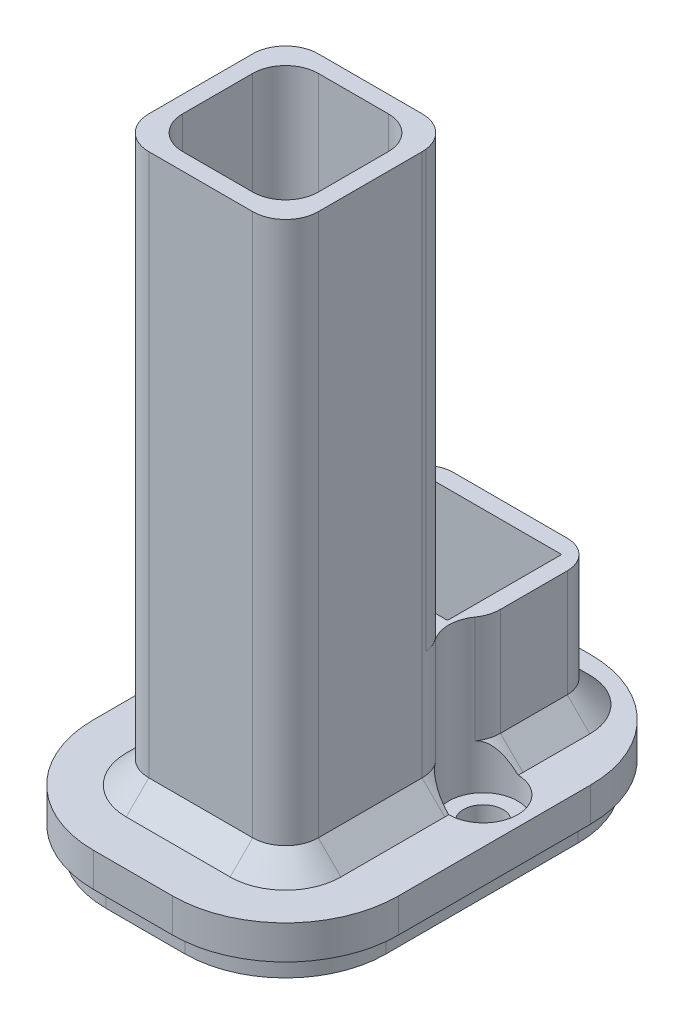
SolidWorks part; units mm, degrees
ref_plane "Front Plane" through (0, 0, 0) normal (0, 0, 1) x (1, 0, 0)
ref_plane "Top Plane" through (0, 0, 0) normal (0, 1, 0) x (1, 0, 0)
ref_plane "Right Plane" through (0, 0, 0) normal (1, 0, 0) x (0, 0, -1)
sketch "Sketch2" plane through (0, 0, 0) normal (0, 1, 0) x (1, 0, 0)
  line L0 (-7.55, 19.89) -> (7.55, 19.89)
  line L1 (-6.05, 8.29) -> (6.05, 8.29)
  line L2 (-6.05, 8.29) -> (-6.05, 18.39)
  line L3 (-6.05, 18.39) -> (6.05, 18.39)
  line L4 (0, -55) -> (0, 55) construction
  line L8 (13.5, -13.5) -> (13.5, 23.5)
  line L9 (13.5, 23.5) -> (-13.5, 23.5)
  line L10 (-13.5, 23.5) -> (-13.5, -13.5)
  line L11 (-13.5, -13.5) -> (13.5, -13.5)
  line L12 (6.05, 8.29) -> (6.05, 18.39)
  line L13 (-6.05, 8.29) -> (6.05, 18.39) construction
  line L14 (-6.05, 18.39) -> (6.05, 8.29) construction
  line L15 (7.55, 6.79) -> (7.55, 19.89)
  line L16 (-7.55, 6.79) -> (7.55, 6.79)
  line L17 (-7.55, 6.79) -> (-7.55, 19.89)
  circle A0 centre (0, 13.34) radius 4.25
  circle A1 centre (0, 0) radius 8.05
  circle A2 centre (-9.5, 8) radius 1.75
  circle A4 centre (9.5, 8) radius 1.75
  circle A5 centre (0, 0) radius 3
  point P2 (0, 13.34)
  point P16 (0, -10.5165)
  point P24 (0, -13.5)
  dimension "D5" = 8.5
  dimension "D6" = 16.1
  dimension "D10" = 8
  dimension "D8" = 3.5
  dimension "D12" = 6
  dimension "D2" = 12.1
  dimension "D3" = 10.1
  dimension "D1" = 37
  dimension "D7" = 27
  dimension "D9" = 10.16
  dimension "D11" = 4
  dimension "D4" = 1.5
extrude "Boss-Extrude1" add sketch "Sketch2" along normal blind 5 contours L10 L11 L8 L9 L16 L17 L0 L15 | L17 A2 | A4 | L16 A1 region at (0, 0, -6.571) region at (0, 0, 13.042) region at (-9.5, 0, -8) region at (9.5, 0, -8)
extrude "Boss-Extrude2" add sketch "Sketch2<7>" along normal blind 16.5 contours A1 L16 L15 L0 L17 L12 L1 L2 L3 | L16 A1 region at (0, 0, -19.6901) region at (0, 0, -7.2975)
sketch "Sketch2<7>" plane through (0, 0, 0) normal (0, 1, 0) x (1, 0, 0) same geometry as "Sketch2"
extrude "Boss-Extrude3" add sketch "Sketch2<8>" along normal blind 1 contours L1 L12 L3 L2 A0 region at (-5.8924, 0, -13.34)
sketch "Sketch2<8>" plane through (0, 0, 0) normal (0, 1, 0) x (1, 0, 0) same geometry as "Sketch2"
extrude "Cut-Extrude3" cut sketch "Sketch2<12>" along normal blind 4 contours L16 A1 | L16 A1 region at (0, 0, -7.2975) region at (0, 0, -6.571)
sketch "Sketch2<12>" plane through (0, 0, 0) normal (0, 1, 0) x (1, 0, 0) same geometry as "Sketch2"
extrude "Cut-Extrude2" cut sketch "Sketch2<11>" along normal through all contours A2 | A4 region at (-9.5, 0, -8) region at (9.5, 0, -8)
sketch "Sketch2<11>" plane through (0, 0, 0) normal (0, 1, 0) x (1, 0, 0) same geometry as "Sketch2"
fillet "Fillet1" radius 10 4 edges at (-13.5, 2.5, -23.5) (-13.5, 2.5, 13.5) (13.5, 2.5, 13.5) (13.5, 2.5, -23.5)
sketch "Sketch3" plane through (0, 0, 0) normal (0, -1, 0) x (1, 0, 0)
  line L4 (-12.4, 3.5) -> (-12.4, -13.5)
  line L5 (-3.5, -22.4) -> (3.5, -22.4)
  line L6 (12.4, -13.5) -> (12.4, 3.5)
  line L7 (3.5, 12.4) -> (-3.5, 12.4)
  line L12 (-13.5, 3.5) -> (-13.5, -13.5)
  line L13 (-3.5, -23.5) -> (3.5, -23.5)
  line L14 (13.5, -13.5) -> (13.5, 3.5)
  line L15 (3.5, 13.5) -> (-3.5, 13.5)
  line L16 (-13.5, 3.5) -> (-13.5, -13.5)
  line L17 (-3.5, -23.5) -> (3.5, -23.5)
  line L18 (13.5, -13.5) -> (13.5, 3.5)
  line L19 (3.5, 13.5) -> (-3.5, 13.5)
  arc A4 (-12.4, -13.5) -> (-3.5, -22.4) centre (-3.5, -13.5) ccw
  arc A5 (3.5, -22.4) -> (12.4, -13.5) centre (3.5, -13.5) ccw
  arc A6 (12.4, 3.5) -> (3.5, 12.4) centre (3.5, 3.5) ccw
  arc A7 (-3.5, 12.4) -> (-12.4, 3.5) centre (-3.5, 3.5) ccw
  arc A12 (-13.5, -13.5) -> (-3.5, -23.5) centre (-3.5, -13.5) ccw
  arc A14 (3.5, -23.5) -> (13.5, -13.5) centre (3.5, -13.5) ccw
  arc A16 (13.5, 3.5) -> (3.5, 13.5) centre (3.5, 3.5) ccw
  arc A17 (-3.5, 13.5) -> (-13.5, 3.5) centre (-3.5, 3.5) ccw
  arc A18 (-13.5, -13.5) -> (-3.5, -23.5) centre (-3.5, -13.5) ccw
  arc A19 (3.5, -23.5) -> (13.5, -13.5) centre (3.5, -13.5) ccw
  arc A20 (13.5, 3.5) -> (3.5, 13.5) centre (3.5, 3.5) ccw
  arc A22 (-3.5, 13.5) -> (-13.5, 3.5) centre (-3.5, 3.5) ccw
  dimension "D1" = 0
  dimension "D2" = 1.1
extrude "Cut-Extrude1" cut sketch "Sketch3" against normal blind 2
sketch "Sketch4" plane through (0, 5, 0) normal (0, 1, 0) x (1, 0, 0)
  line L0 (7.5, -7.5) -> (7.5, 7.5)
  line L1 (-6, -6) -> (6, -6)
  line L2 (-6, -6) -> (-6, 6)
  line L3 (-6, 6) -> (6, 6)
  line L4 (6, -6) -> (6, 6)
  line L5 (-6, -6) -> (6, 6) construction
  line L6 (-6, 6) -> (6, -6) construction
  line L7 (-7.5, 7.5) -> (7.5, 7.5)
  line L8 (-7.5, -7.5) -> (-7.5, 7.5)
  line L9 (-7.5, -7.5) -> (7.5, -7.5)
  line L10 (0, -9.075) -> (0, 9.075) construction
  circle A0 centre (-9.5, 8) radius 3.05
  circle A1 centre (9.5, 8) radius 3.05
  point P0 (0, 0)
  line M6 (7.55, 19.89) -> (7.55, 6.79)
  line M7 (7.55, 6.79) -> (-7.55, 6.79)
  line M8 (-7.55, 6.79) -> (-7.55, 19.89)
  circle M18 centre (9.5, 8) radius 1.75
  circle M19 centre (-9.5, 8) radius 1.75
  dimension "D3" = 6.1
  dimension "D1" = 12
  dimension "D2" = 1.5
extrude "Boss-Extrude8" add sketch "Sketch4" along normal blind 50 contours A1 L7 A0 M7 | A0 L7 L8 M7 | L8 A0 M7 | A1 L0 L7 M7 | A1 L0 M7 | L0 A1 A0 L8 L9 L4 L1 L2 L3 M7 region at (0, 5, 7.2928) region at (7.2119, 5, -6.3985) region at (7.0381, 5, -7.1584) region at (0, 5, -7.1431) region at (-7.2119, 5, -6.3985) region at (-7.0381, 5, -7.1584)
fillet "Fillet4" radius 2.5 4 edges at (-7.55, 10.75, -19.89) (7.55, 10.75, -19.89) (7.55, 10.75, -6.79) (-7.55, 10.75, -6.79)
extrude "Cut-Extrude4" cut sketch "Sketch4<3>" against normal blind 2 and the other way blind 22 contours A1 L0 M6 M7 M18 | A1 L7 L0 M7 M6 | A1 L0 L7 M7 | A1 L0 M7 | L7 A0 L8 M8 M7 | A0 L7 L8 M7 | A0 L8 M8 M7 M19 | L8 A0 M7 region at (7.2119, 5, -6.3985) region at (7.5792, 5, -6.2436) region at (7.0381, 5, -7.1584) region at (7.0868, 5, -8.6148) region at (-12.4706, 5, -7.968) region at (-7.2119, 5, -6.3985) region at (-7.0381, 5, -7.1584) region at (-7.0868, 5, -8.6148)
sketch "Sketch4<3>" plane through (0, 5, 0) normal (0, 1, 0) x (1, 0, 0) same geometry as "Sketch4"
fillet "Fillet3" radius 2.9 4 edges at (7.5, 41, -7.5) (-7.5, 41, -7.5) (7.5, 30, 7.5) (-7.5, 30, 7.5)
fillet "Fillet5" radius 3 4 edges at (-7.55, 10.75, -10.3452) (-7.5, 10.75, -5.6973) (7.55, 10.75, -10.3452) (7.5, 10.75, -5.6973)
chamfer "Chamfer1" distance 2 angle 45 14 edges at (-7.4104, 5, -10.574) (-7.55, 5, -14.4343) (-6.8178, 5, -19.1578) (0, 5, -19.89) (7.4104, 5, -10.574) (6.8178, 5, -19.1578) (7.55, 5, -14.4343) (-7.3669, 5, -5.4775) (-7.5, 5, 0.0031) (-6.6506, 5, 6.6506) (0, 5, 7.5) (6.6506, 5, 6.6506) (7.3669, 5, -5.4775) (7.5, 5, 0.0031)
fillet "Fillet6" radius 2.9 4 edges at (-6, 30, 6) (6, 30, 6) (6, 30, -6) (-6, 30, -6)
